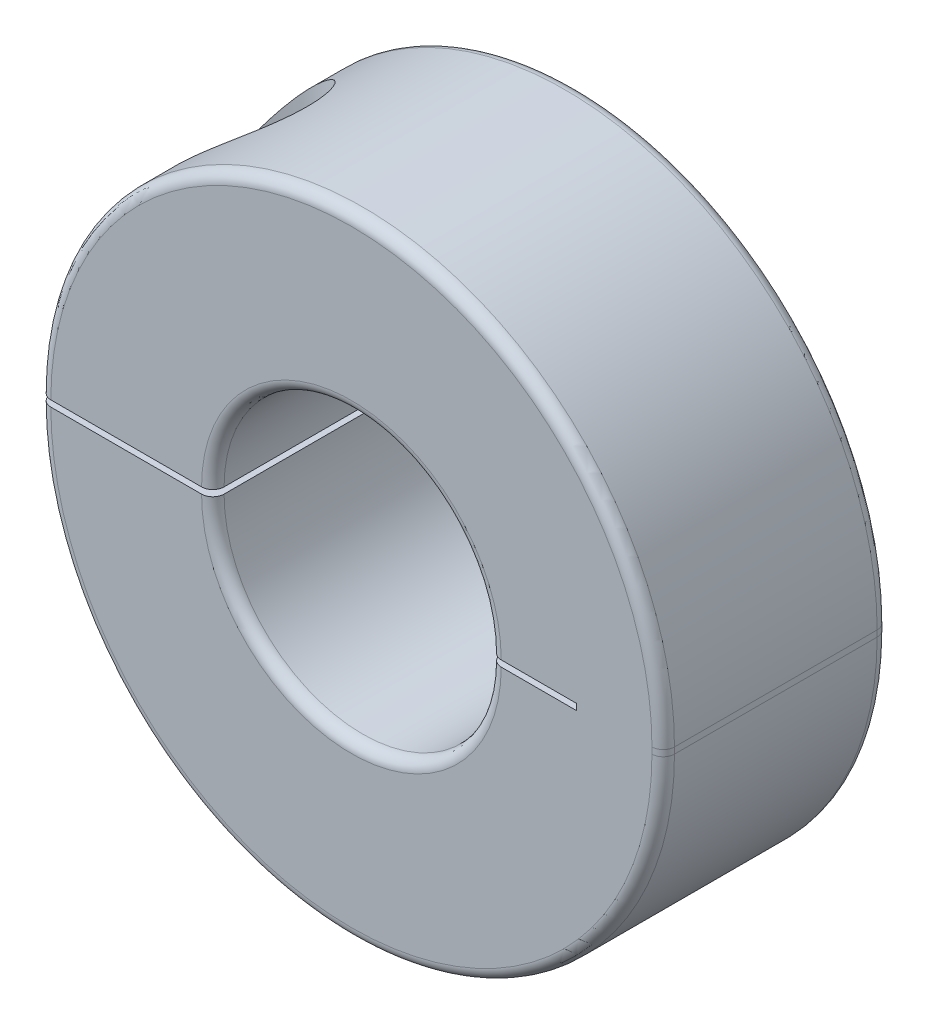
SolidWorks part; units mm, degrees
material "6061-T6 (SS)"
ref_plane "Front Plane" through (0, 0, 0) normal (0, 0, 1) x (1, 0, 0)
ref_plane "Top Plane" through (0, 0, 0) normal (0, 1, 0) x (1, 0, 0)
ref_plane "Right Plane" through (0, 0, 0) normal (1, 0, 0) x (0, 0, -1)
sketch "Sketch1" plane through (0, 0, 0) normal (0, 0, 1) x (1, 0, 0)
  line L0 (-14.2875, 0) -> (-6.35, 0) construction
  line L1 (-14.2875, 0.1429) -> (-6.35, 0.1429)
  line L2 (-14.2875, -0.1429) -> (-6.35, -0.1429)
  line L3 (6.35, 0.1429) -> (14.2875, 0.1429) construction
  line L4 (6.35, -0.1429) -> (14.2875, -0.1429) construction
  line L5 (0, 0) -> (0, 14.2875) construction
  line L6 (14.2875, 0.1429) -> (14.2875, -0.1429)
  line L7 (6.35, 0.1429) -> (10.3188, 0.1429)
  line L8 (10.3188, 0.1429) -> (10.3188, -0.1429)
  line L10 (10.3188, -0.1429) -> (6.35, -0.1429)
  circle A0 centre (0, 0) radius 14.2875 construction
  circle A1 centre (0, 0) radius 6.35 construction
  arc A2 (-14.2875, 0.1429) -> (14.2875, 0.1429) centre (0, 0.1429) cw
  arc A3 (-14.2875, -0.1429) -> (14.2875, -0.1429) centre (0, -0.1429) ccw
  arc A4 (-6.35, 0.1429) -> (6.35, 0.1429) centre (0, 0.1429) cw
  arc A5 (-6.35, -0.1429) -> (6.35, -0.1429) centre (0, -0.1429) ccw
  point P4 (14.2875, 0)
  dimension "Bore Dia" = 12.7
  dimension "OD" = 28.575
  dimension "Separation" = 0.2858
extrude "Extrude1" add sketch "Sketch1" along normal mid plane 10.3187
sketch "Sketch4" plane through (0, 0, 0) normal (0, 0, 1) x (1, 0, 0)
  line L0 (-10.3188, 14.4304) -> (-7.1946, 14.4304)
  line L1 (-7.1946, 14.4304) -> (-7.1946, 2.2257)
  line L2 (-7.1946, 2.2257) -> (-8.236, 2.2257)
  line L3 (-8.236, 2.2257) -> (-8.236, -14.4304)
  line L4 (-8.236, -14.4304) -> (-10.3188, -14.4304)
  line L5 (-10.3188, -14.4304) -> (-10.3188, 14.4304)
  line L6 (-7.1946, 6.3913) -> (-13.443, 6.3913) construction
  line L7 (-10.3188, 14.4304) -> (-10.3188, 16.9704) construction
  line L8 (-7.1946, 14.4304) -> (0, 14.4304) construction
  line L9 (0, -14.4304) -> (-8.236, -14.4304) construction
  line L10 (-14.2875, 0) -> (-6.35, 0) construction
  line L11 (-14.2875, 0.1429) -> (-6.35, 0.1429) construction
  circle A0 centre (0, 0) radius 14.2875 construction
  arc A1 (14.2875, 0.1429) -> (-14.2875, 0.1429) centre (0, 0.1429) ccw construction
  circle A2 centre (0, 0) radius 6.35 construction
  arc A3 (-14.2875, -0.1429) -> (14.2875, -0.1429) centre (0, -0.1429) ccw construction
  point P13 (-10.3188, 0)
  point P19 (-10.3188, 0)
  point P20 (-10.3188, 6.3913)
  dimension "D1" = 4.1656
  dimension "D2" = 7.9375
  dimension "D3" = 2.0828
  dimension "D4" = 6.2484
  dimension "D5" = 2.54
  dimension "Screw Dia" = 4.1656
revolve "Cut-Revolve1" cut sketch "Sketch4" angle 360 about L5
sketch "Sketch6" plane through (0, 0, 0) normal (0, 0, 1) x (1, 0, 0)
  line L0 (-10.3188, 6.3913) -> (-7.1946, 6.3913)
  line L1 (-7.1946, 6.3913) -> (-13.443, 6.3913) construction
  line L2 (-7.1946, 6.3913) -> (-7.1946, 2.2257)
  line L3 (-7.1946, 2.2257) -> (-8.236, 2.2257)
  line L4 (-8.236, 2.2257) -> (-8.236, -6.1055)
  line L5 (-8.236, 2.2257) -> (-8.236, -14.4304) construction
  line L6 (-8.236, -6.1055) -> (-10.3188, -6.1055)
  line L7 (-10.3188, -14.4304) -> (-10.3188, 14.4304) construction
  line L8 (-10.3188, -6.1055) -> (-10.3188, 6.3913)
  line L9 (-8.236, -6.1055) -> (-12.4016, -6.1055) construction
  dimension "Head Ht" = 4.1656
  dimension "Screw Lg" = 12.4968
revolve "Revolve1" add sketch "Sketch6" angle 360 about L8
sketch "Sketch7" plane through (0, 6.3913, 0) normal (0, 1, 0) x (-1, 0, 0)
  line L1 (10.3188, -1.924) -> (11.985, -0.962)
  line L2 (11.985, -0.962) -> (11.985, 0.962)
  line L3 (11.985, 0.962) -> (10.3188, 1.924)
  line L4 (10.3188, 1.924) -> (8.6525, 0.962)
  line L5 (8.6525, 0.962) -> (8.6525, -0.962)
  line L6 (8.6525, -0.962) -> (10.3188, -1.924)
  circle A0 centre (10.3188, 0) radius 1.6662 construction
  dimension "D1" = 3.3325
extrude "Cut-Extrude2" cut sketch "Sketch7" against normal blind 2.0828
fillet "Fillet1" radius 0.5159 8 edges at (0, 6.4929, -5.1594) (0, 6.4929, 5.1594) (0, 14.4304, -5.1594) (0, 14.4304, 5.1594) (0, -14.4304, -5.1594) (0, -14.4304, 5.1594) (14.2875, 0, -5.1594) (14.2875, 0, 5.1594)
fillet "Fillet2" radius 0.5159 2 edges at (0, -6.4929, -5.1594) (0, -6.4929, 5.1594)
chamfer "Chamfer2" distance 0.254 angle 45 1 edges at (-10.3188, 6.3913, -3.1242)
equation "\"D1@Sketch4\" = \"Screw Dia@Sketch4\""
equation "\"D4@Sketch4\" = \"Screw Dia@Sketch4\"*1.5"
equation "\"D1@Sketch7\" = \"Screw Dia@Sketch4\"*.8"
equation "\"D1@Cut-Extrude2\" = \"Head Ht@Sketch6\"/2"
equation "\"D3@Sketch4\" = \"D1@Sketch4\"*.5"
equation "\"D1@Fillet1\" = \"Width@Extrude1\"*.05"
equation "\"D1@Fillet2\" = \"D1@Fillet1\""
equation "\"Screw Lg@Sketch6\" = \"Head Ht@Sketch6\"*3"
equation "\"Separation@Sketch1\" = \"OD@Sketch1\"*.01"
